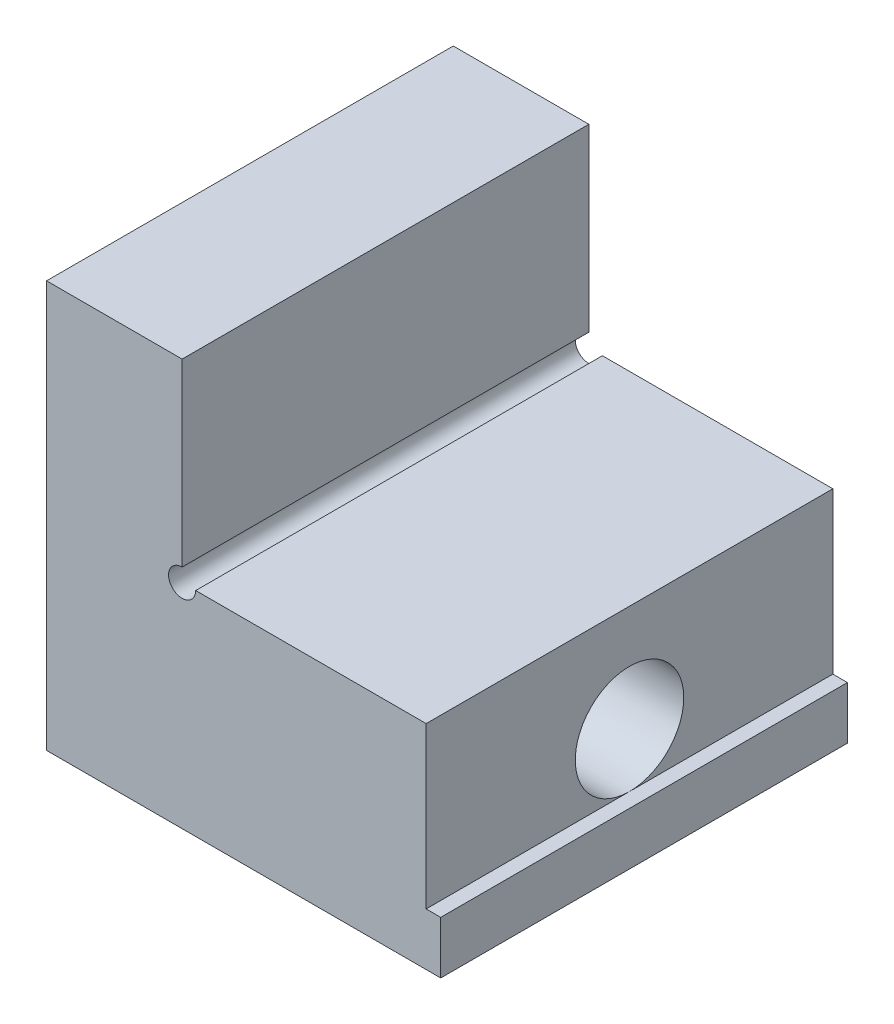
SolidWorks part; units mm, degrees
ref_plane "Front Plane" through (0, 0, 0) normal (0, 0, 1) x (1, 0, 0)
ref_plane "Top Plane" through (0, 0, 0) normal (0, 1, 0) x (1, 0, 0)
ref_plane "Right Plane" through (0, 0, 0) normal (1, 0, 0) x (0, 0, -1)
sketch "Sketch1" plane through (0, 0, 0) normal (0, 0, 1) x (1, 0, 0)
  line L0 (-10, -15.715) -> (-10, 14.285)
  line L1 (-10, 14.285) -> (0, 14.285)
  line L2 (0, 14.285) -> (0, 1)
  line L3 (1, 0) -> (18, 0)
  line L5 (19.0754, -15.715) -> (-10, -15.715)
  line L6 (0, 1) -> (0, 0) construction
  line L7 (0, 0) -> (1, 0) construction
  line L11 (18, 0) -> (18, -11.84)
  line L12 (19.0754, -11.84) -> (19.0754, -15.715)
  line L13 (18, -11.84) -> (19.0754, -11.84)
  line L14 (0, 0) -> (0, -7.84) construction
  line L15 (0, -7.84) -> (13.932, -7.84) construction
  line L16 (13.932, -7.84) -> (13.932, -11.84) construction
  line L17 (13.932, -11.84) -> (18, -11.84) construction
  arc A0 (0, 1) -> (1, 0) centre (0, 0) ccw
  dimension "D4" = 2
  dimension "D1" = 18
  dimension "D2" = 10
  dimension "D3" = 30
  dimension "D5" = 15.715
  dimension "D7" = 7.84
  dimension "D8" = 4
  dimension "D9" = 19.0754
extrude "Boss-Extrude1" add sketch "Sketch1" against normal blind 15 and the other way blind 15 contours A0 L2 L1 L0 L5 L3 region at (1.9214, -4.2659, 0)
sketch "Sketch2" plane through (0, 0, 0) normal (1, 0, 0) x (0, 0, -1)
  line L3 (0, 0) -> (0, -7.84) construction
  circle A1 centre (0, -7.84) radius 4
  point P0 (0.4281, -7.84)
  point P1 (0, 0)
  dimension "D2" = 8
  dimension "D1" = 7.84
extrude "Cut-Extrude1" cut sketch "Sketch2" along normal blind 55.4 and the other way blind 30
sketch "Sketch3" plane through (0, 0, 0) normal (1, 0, 0) x (0, 0, -1)
  circle A1 centre (0, -7.84) radius 6.5
  dimension "D1" = 13
extrude "Cut-Extrude2" cut sketch "Sketch3" against normal blind 18.2
